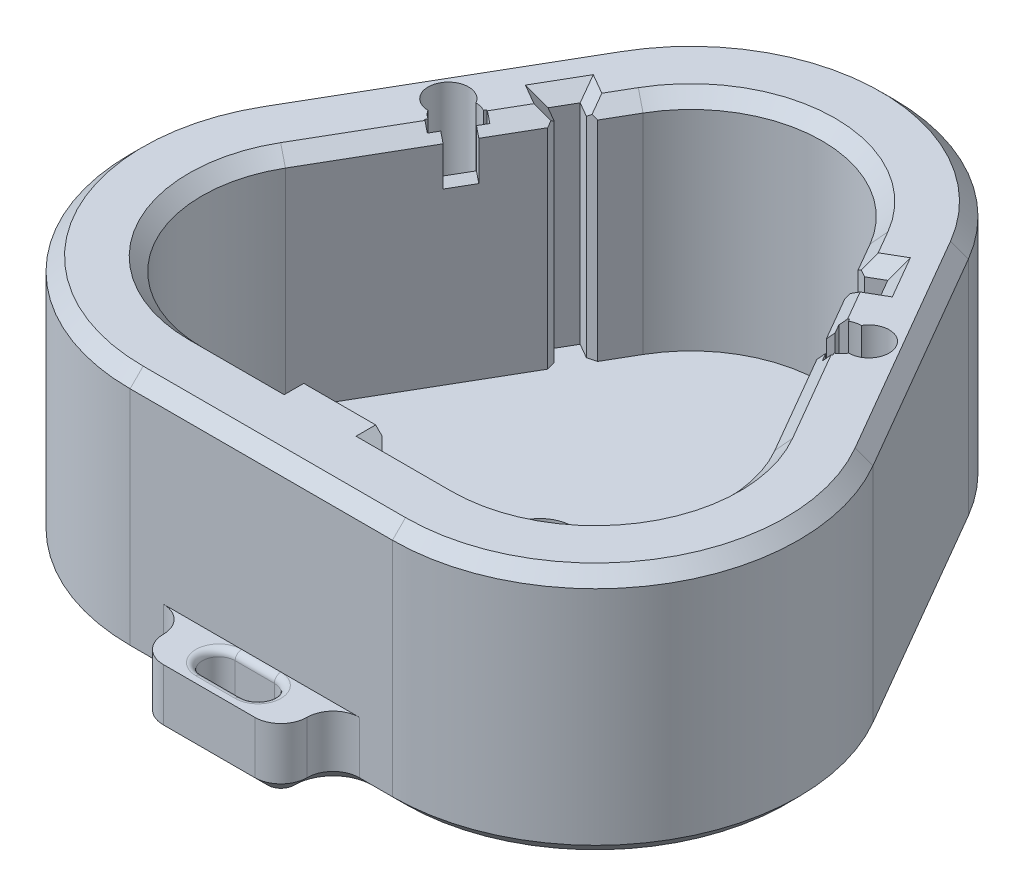
SolidWorks part; units mm, degrees
ref_plane "Front Plane" through (0, 0, 0) normal (0, 0, 1) x (1, 0, 0)
ref_plane "Top Plane" through (0, 0, 0) normal (0, 1, 0) x (1, 0, 0)
ref_plane "Right Plane" through (0, 0, 0) normal (1, 0, 0) x (0, 0, -1)
sketch "Sketch1" plane through (0, 0, 0) normal (0, 1, 0) x (1, 0, 0)
  line L0 (0, 11.5518) -> (-10.0362, -5.7759) construction
  line L1 (-10.0362, -5.7759) -> (10.0362, -5.7759) construction
  line L2 (10.0362, -5.7759) -> (0, 11.5518) construction
  line L3 (-10.0362, -5.7759) -> (5.0181, 2.8879) construction
  line L4 (-5.0181, 2.8879) -> (10.0362, -5.7759) construction
  line L5 (-8.6846, 16.5819) -> (-18.7208, -0.7458)
  line L6 (-10.0362, -15.8121) -> (10.0362, -15.8121)
  line L7 (8.6846, 16.5819) -> (18.7208, -0.7458)
  line L8 (0, 21.5879) -> (0, -15.8121) construction
  line L9 (-13.4439, 19.3385) -> (-23.4801, 2.0108)
  line L10 (-10.0362, -21.3121) -> (10.0362, -21.3121)
  line L11 (13.4439, 19.3385) -> (23.4801, 2.0108)
  line L25 (-3.75, -15.3121) -> (3.75, -15.3121)
  line L26 (-3.75, -15.8121) -> (-3.75, -15.3121)
  line L27 (3.75, -15.3121) -> (3.75, -15.8121)
  line L28 (0, -15.2648) -> (0, -15.7648) construction
  line L29 (-3.75, -15.8121) -> (3.75, -15.8121)
  line L34 (8.6846, 16.5819) -> (18.7208, -0.7458) construction
  line L35 (-8.6846, 16.5819) -> (-18.7208, -0.7458) construction
  line L36 (-10.2087, 13.9505) -> (-11.7663, 14.8527)
  line L37 (-11.7663, 14.8527) -> (-12.6685, 13.2951)
  line L38 (-12.6685, 13.2951) -> (-11.1109, 12.3929)
  line L39 (-11.1109, 12.3929) -> (-10.2087, 13.9505)
  line L40 (10.2087, 13.9505) -> (11.7663, 14.8527)
  line L41 (11.7663, 14.8527) -> (12.6685, 13.2951)
  line L42 (12.6685, 13.2951) -> (11.1109, 12.3929)
  line L43 (-13.3501, 9.5244) -> (-15.1043, 6.4957)
  line L44 (-15.1043, 6.4957) -> (-15.6235, 6.7965)
  line L45 (-15.6235, 6.7965) -> (-13.8693, 9.8251)
  line L46 (-13.8693, 9.8251) -> (-13.3501, 9.5244)
  line L47 (13.8693, 9.8251) -> (13.3501, 9.5244)
  line L48 (15.1043, 6.4957) -> (15.6235, 6.7965)
  line L49 (15.6235, 6.7965) -> (13.8693, 9.8251)
  line L50 (13.3501, 9.5244) -> (15.1043, 6.4957)
  arc A1 (-18.7208, -0.7458) -> (-10.0362, -15.8121) centre (-10.0362, -5.7759) ccw
  arc A2 (10.0362, -15.8121) -> (18.7208, -0.7458) centre (10.0362, -5.7759) ccw
  arc A5 (8.6846, 16.5819) -> (-8.6846, 16.5819) centre (0, 11.5518) ccw
  arc A6 (13.4439, 19.3385) -> (-13.4439, 19.3385) centre (0, 11.5518) ccw
  arc A7 (-23.4801, 2.0108) -> (-10.0362, -21.3121) centre (-10.0362, -5.7759) ccw
  arc A8 (10.0362, -21.3121) -> (23.4801, 2.0108) centre (10.0362, -5.7759) ccw
  arc A9 (-13.9696, 9.6521) -> (-15.5233, 6.9695) centre (-14.7464, 8.3108) ccw
  arc A10 (13.9696, 9.6521) -> (15.5233, 6.9695) centre (14.7464, 8.3108) cw
  circle A11 centre (-16.0877, 9.0877) radius 1.55
  circle A12 centre (16.0877, 9.0877) radius 1.55
  point P5 (0, 21.5879)
  point P7 (0, 0)
  point P28 (0, -15.3121)
  point P50 (0, 0)
  dimension "D1" = 37.4
  dimension "D2" = 5.5
  dimension "D8" = 3.1
  dimension "D3" = 3.5
  dimension "D4" = 20.0723
  dimension "D5" = 1.8
  dimension "D7" = 3.0409
  dimension "D9" = 0.6
  dimension "D10" = 0.5
  dimension "D11" = 0.5
  dimension "D12" = 5.3545
  dimension "D6" = 7.5
extrude "Boss-Extrude1" add sketch "Sketch1" along normal blind 17 contours L10 A8 L11 A6 L9 A7 A9 L45 L46 L43 L44 A5 L7 L40 L41 L42 A2 L6 A1 L5 L38 L37 L36 L49 A10 L48 L50 L47 | L27 L25 L26 L6 region at (0, 0, 15.5621) region at (0, 0, -26.3838)
chamfer "Chamfer1" distance 0.5 angle 45 4 edges at (10.2087, 8.5, -13.9505) (-10.2087, 8.5, -13.9505) (11.1109, 8.5, -12.3929) (-11.1109, 8.5, -12.3929) tangent propagation no
extrude "Boss-Extrude2" add sketch "Sketch1<4>" against normal blind 2 contours A9 A11 | A11 A9 | A10 A12 | A10 A12 | L11 A8 L10 A7 L9 A6 region at (-15.4171, 0, -8.6992) region at (-16.5183, 0, -9.337) region at (15.4171, 0, -8.6992) region at (16.5183, 0, -9.337)
sketch "Sketch1<4>" plane through (0, 0, 0) normal (0, 1, 0) x (1, 0, 0) same geometry as "Sketch1"
sketch "Sketch2" plane through (0, -2, 0) normal (0, -1, 0) x (1, 0, 0)
  line L0 (5.5, 21.3121) -> (5.5, 25.3121)
  line L5 (5.5, 25.3121) -> (-5.5, 25.3121)
  line L6 (-5.5, 25.3121) -> (-5.5, 21.3121)
  line L7 (-5.5, 21.3121) -> (5.5, 21.3121)
  line L8 (-1.5, 23.0621) -> (1.5, 23.0621) construction
  line L9 (-1.5, 24.3121) -> (1.5, 24.3121)
  line L10 (-1.5, 21.8121) -> (1.5, 21.8121)
  line L11 (-10.0362, 21.3121) -> (10.0362, 21.3121) construction
  arc A6 (-1.5, 24.3121) -> (-1.5, 21.8121) centre (-1.5, 23.0621) ccw
  arc A7 (1.5, 21.8121) -> (1.5, 24.3121) centre (1.5, 23.0621) ccw
  circle A8 centre (0, 0) radius 2.5
  point P0 (5.5, 21.3121)
  point P2 (0, 21.3121)
  point P18 (0, 25.3121)
  point P21 (0, 23.0621)
  dimension "D4" = 5.5
  dimension "D6" = 5
  dimension "D1" = 11
  dimension "D2" = 4
  dimension "D3" = 2.5
  dimension "D5" = 0.5
extrude "Cut-Extrude2" cut sketch "Sketch2" against normal up to next contours A8 region at (0, -2, 0)
extrude "Boss-Extrude3" add sketch "Sketch2<2>" against normal blind 5 contours L5 L6 L0 A7 L10 A6 L9 region at (0, -2, 21.4291)
sketch "Sketch2<2>" plane through (0, -2, 0) normal (0, -1, 0) x (1, 0, 0) same geometry as "Sketch2"
fillet "Fillet1" radius 2 4 edges at (5.5, 0.5, 21.3121) (5.5, 0.5, 25.3121) (-5.5, 0.5, 25.3121) (-5.5, 0.5, 21.3121)
fillet "Fillet2" radius 0.5 4 edges at (0, 3, 24.3121) (2.75, 3, 23.0621) (0, 3, 21.8121) (-2.75, 3, 23.0621)
chamfer "Chamfer4" distance 1 angle 45 18 edges at (0, -2, 25.3121) (18.462, 17, -10.6747) (0, 17, -27.0879) (23.4963, 17, 13.5346) (-18.462, 17, -10.6747) (0, 17, 21.3121) (-23.4963, 17, 13.5346) (6.0858, -2, 21.8978) (8.7681, -2, 21.3121) (4.9142, -2, 24.7263) (23.4963, -2, 13.5346) (18.462, -2, -10.6747) (-4.9142, -2, 24.7263) (0, -2, -27.0879) (-6.0858, -2, 21.8978) (-18.462, -2, -10.6747) (-8.7681, -2, 21.3121) (-23.4963, -2, 13.5346)
sketch "Sketch3" plane through (0, 17, 0) normal (0, 1, 0) x (1, 0, 0)
  line L0 (-13.726, 8.8754) -> (-13.2934, 8.6248)
  line L2 (-13.2934, 8.6248) -> (-14.2958, 6.8941)
  line L3 (-11.3615, 11.9602) -> (-18.7208, -0.7458) construction
  line L4 (-14.2958, 6.8941) -> (-14.7284, 7.1447)
  line L5 (-14.7284, 7.1447) -> (-13.726, 8.8754)
  line L6 (-13.3501, 9.5244) -> (-15.1043, 6.4957) construction
  line L7 (0, -10.45) -> (0, 10.45) construction
  line L8 (14.7284, 7.1447) -> (13.726, 8.8754)
  line L9 (14.2958, 6.8941) -> (14.7284, 7.1447)
  line L10 (13.2934, 8.6248) -> (14.2958, 6.8941)
  line L11 (13.726, 8.8754) -> (13.2934, 8.6248)
  line L12 (-11.3615, 11.9602) -> (-18.7208, -0.7458) construction
  point P3 (-13.0066, 8.2432)
  point P10 (-14.2272, 8.0101)
  point P17 (0, 0)
  dimension "D1" = 2
extrude "Cut-Extrude3" cut sketch "Sketch3" against normal blind 3
chamfer "Chamfer5" distance 1 angle 45 21 edges at (13.7946, 14, -7.7595) (-13.7946, 14, -7.7595) (11.2039, 17, -14.5269) (12.2174, 17, -14.0739) (12.106, 17, -12.9693) (12.3274, 17, -10.2925) (16.5083, 17, -3.0742) (18.7312, 17, 10.7879) (6.8931, 17, 15.8121) (3.75, 17, 15.5621) (-3.75, 17, 15.5621) (-6.8931, 17, 15.8121) (-18.7312, 17, 10.7879) (-16.5083, 17, -3.0742) (-12.3274, 17, -10.2925) (-12.106, 17, -12.9693) (-11.2039, 17, -14.5269) (-12.2174, 17, -14.0739) (9.3214, 17, -15.4825) (-9.3214, 17, -15.4825) (0, 17, -21.5879)
chamfer "Chamfer6" distance 0.5 angle 45 2 edges at (3.75, 8, 15.3121) (-3.75, 8, 15.3121)
